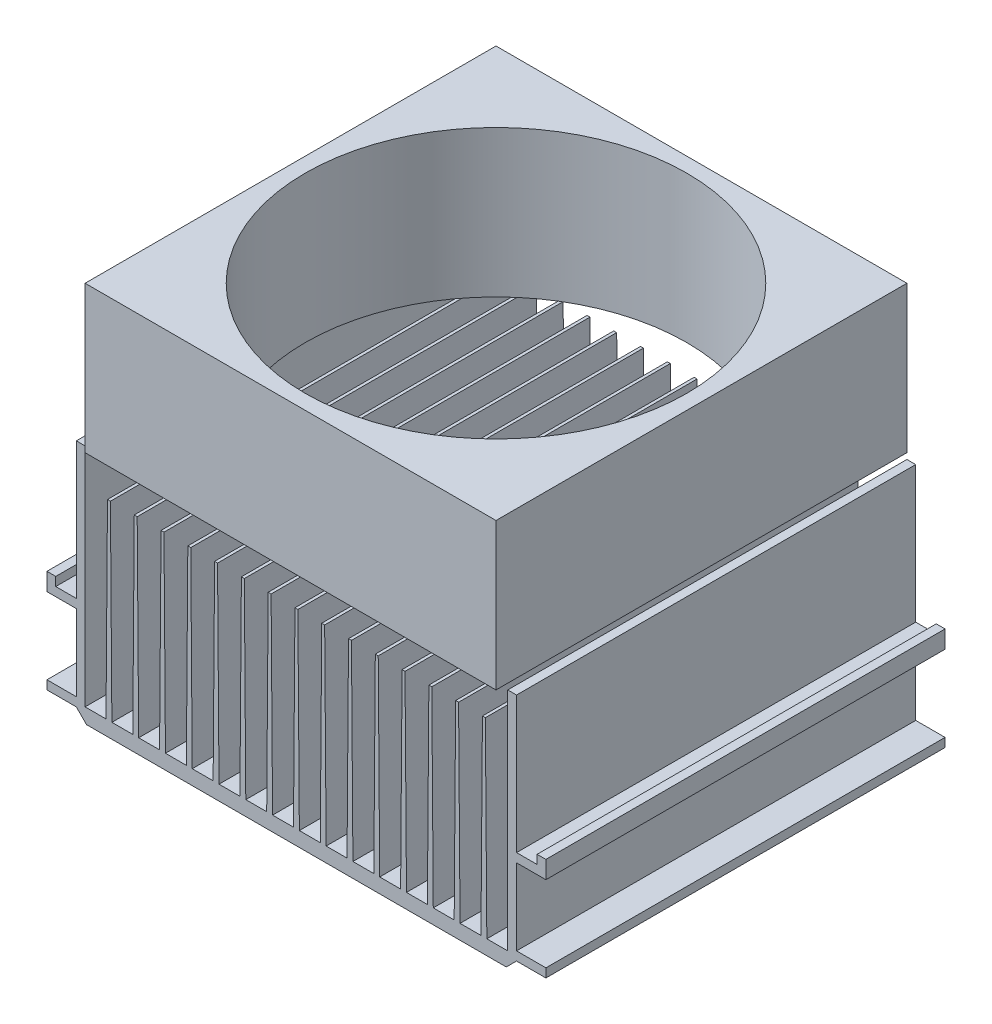
SolidWorks part; units mm, degrees
material "1060 Alloy"
ref_plane "Front Plane" through (0, 0, 0) normal (0, 0, 1) x (1, 0, 0)
ref_plane "Top Plane" through (0, 0, 0) normal (0, 1, 0) x (1, 0, 0)
ref_plane "Right Plane" through (0, 0, 0) normal (1, 0, 0) x (0, 0, -1)
sketch "Sketch1" plane through (0, 0, 0) normal (0, 0, 1) x (1, 0, 0)
  line L0 (0, 0) -> (0, 21.4242) construction
  line L1 (-35.75, 0) -> (35.75, 0)
  line L2 (35.75, 0) -> (37.5, 1.75)
  line L3 (37.5, 1.75) -> (42.5, 1.75)
  line L4 (42.5, 1.75) -> (42.5, 3.25)
  line L5 (42.5, 3.25) -> (37.5, 3.25)
  line L6 (37.5, 3.25) -> (37.5, 16.25)
  line L7 (37.5, 41) -> (36, 41)
  line L8 (36, 41) -> (36, 2.5)
  line L9 (36, 2.5) -> (32.4375, 2.5)
  line L10 (32.4375, 2.5) -> (32.1875, 35)
  line L11 (32.1875, 35) -> (31.6875, 35)
  line L12 (31.6875, 35) -> (31.4375, 2.5)
  line L13 (31.4375, 2.5) -> (27.875, 2.5)
  line L14 (31.6875, 35) -> (31.6875, 2.5) construction
  line L15 (31.6875, 2.5) -> (31.4375, 2.5) construction
  line L16 (32.1875, 35) -> (32.1875, 2.5) construction
  line L17 (32.1875, 2.5) -> (32.4375, 2.5) construction
  line L18 (31.6875, 2.5) -> (32.1875, 2.5) construction
  line L19 (37.5, 16.25) -> (42.5, 16.25)
  line L20 (42.5, 16.25) -> (42.5, 19.25)
  line L21 (42.5, 19.25) -> (41, 19.25)
  line L22 (41, 19.25) -> (41, 17.75)
  line L23 (41, 17.75) -> (37.5, 17.75)
  line L24 (37.5, 17.75) -> (37.5, 41)
  line L25 (37.5, 17.75) -> (37.5, 16.25) construction
  line L26 (37.5, 3.25) -> (37.5, 2.5) construction
  line L27 (37.5, 2.5) -> (37.5, 1.75) construction
  line L28 (37.5, 2.5) -> (36, 2.5) construction
  line L29 (27.875, 2.5) -> (27.625, 35)
  line L30 (27.125, 35) -> (26.875, 2.5)
  line L31 (27.625, 35) -> (27.125, 35)
  line L32 (26.875, 2.5) -> (23.3125, 2.5)
  line L33 (23.3125, 2.5) -> (23.0625, 35)
  line L34 (22.5625, 35) -> (22.3125, 2.5)
  line L35 (23.0625, 35) -> (22.5625, 35)
  line L36 (22.3125, 2.5) -> (18.75, 2.5)
  line L37 (18.75, 2.5) -> (18.5, 35)
  line L38 (18, 35) -> (17.75, 2.5)
  line L39 (18.5, 35) -> (18, 35)
  line L40 (17.75, 2.5) -> (14.1875, 2.5)
  line L41 (14.1875, 2.5) -> (13.9375, 35)
  line L42 (13.4375, 35) -> (13.1875, 2.5)
  line L43 (13.9375, 35) -> (13.4375, 35)
  line L44 (13.1875, 2.5) -> (9.625, 2.5)
  line L45 (9.625, 2.5) -> (9.375, 35)
  line L46 (8.875, 35) -> (8.625, 2.5)
  line L47 (9.375, 35) -> (8.875, 35)
  line L48 (8.625, 2.5) -> (5.0625, 2.5)
  line L49 (5.0625, 2.5) -> (4.8125, 35)
  line L50 (4.3125, 35) -> (4.0625, 2.5)
  line L51 (4.8125, 35) -> (4.3125, 35)
  line L52 (0.5, 2.5) -> (0, 2.5) construction
  line L53 (0, 2.5) -> (-0.5, 2.5) construction
  line L54 (4.0625, 2.5) -> (0.5, 2.5)
  line L55 (0.5, 2.5) -> (0.25, 35)
  line L56 (-0.25, 35) -> (-0.5, 2.5)
  line L57 (0.25, 35) -> (-0.25, 35)
  line L58 (-4.0625, 2.5) -> (-0.5, 2.5)
  line L59 (-4.3125, 35) -> (-4.0625, 2.5)
  line L60 (-4.8125, 35) -> (-4.3125, 35)
  line L61 (-5.0625, 2.5) -> (-4.8125, 35)
  line L62 (-8.625, 2.5) -> (-5.0625, 2.5)
  line L63 (-8.875, 35) -> (-8.625, 2.5)
  line L64 (-9.375, 35) -> (-8.875, 35)
  line L65 (-9.625, 2.5) -> (-9.375, 35)
  line L66 (-13.1875, 2.5) -> (-9.625, 2.5)
  line L67 (-13.4375, 35) -> (-13.1875, 2.5)
  line L68 (-13.9375, 35) -> (-13.4375, 35)
  line L69 (-14.1875, 2.5) -> (-13.9375, 35)
  line L70 (-17.75, 2.5) -> (-14.1875, 2.5)
  line L71 (-18, 35) -> (-17.75, 2.5)
  line L72 (-18.5, 35) -> (-18, 35)
  line L73 (-18.75, 2.5) -> (-18.5, 35)
  line L74 (-22.3125, 2.5) -> (-18.75, 2.5)
  line L75 (-22.5625, 35) -> (-22.3125, 2.5)
  line L76 (-23.0625, 35) -> (-22.5625, 35)
  line L77 (-23.3125, 2.5) -> (-23.0625, 35)
  line L78 (-26.875, 2.5) -> (-23.3125, 2.5)
  line L79 (-27.125, 35) -> (-26.875, 2.5)
  line L80 (-27.625, 35) -> (-27.125, 35)
  line L81 (-27.875, 2.5) -> (-27.625, 35)
  line L82 (-31.4375, 2.5) -> (-27.875, 2.5)
  line L83 (-31.6875, 35) -> (-31.4375, 2.5)
  line L84 (-32.1875, 35) -> (-31.6875, 35)
  line L85 (-32.4375, 2.5) -> (-32.1875, 35)
  line L86 (-36, 2.5) -> (-32.4375, 2.5)
  line L87 (-36, 41) -> (-36, 2.5)
  line L88 (-37.5, 41) -> (-36, 41)
  line L89 (-37.5, 17.75) -> (-37.5, 41)
  line L90 (-41, 17.75) -> (-37.5, 17.75)
  line L91 (-41, 19.25) -> (-41, 17.75)
  line L92 (-42.5, 19.25) -> (-41, 19.25)
  line L93 (-42.5, 16.25) -> (-42.5, 19.25)
  line L94 (-37.5, 16.25) -> (-42.5, 16.25)
  line L95 (-37.5, 3.25) -> (-37.5, 16.25)
  line L96 (-42.5, 3.25) -> (-37.5, 3.25)
  line L97 (-42.5, 1.75) -> (-42.5, 3.25)
  line L98 (-37.5, 1.75) -> (-42.5, 1.75)
  line L99 (-35.75, 0) -> (-37.5, 1.75)
  point P96 (0, 0)
  dimension "D1" = 42.5
  dimension "D2" = 41
  dimension "D3" = 2.5
  dimension "D4" = 1.5
  dimension "D5" = 1.5
  dimension "D6" = 5
  dimension "D8" = 0.5
  dimension "D9" = 1
  dimension "D10" = 45
  dimension "D11" = 35
  dimension "D12" = 16
  dimension "D13" = 8
extrude "Heatsink" add sketch "Sketch1" against normal blind 68
sketch "Sketch3" plane through (0, 41, 0) normal (0, 1, 0) x (1, 0, 0)
  line L0 (0, 0) -> (0, 1.5243) construction
  line L1 (-35, 69) -> (35, 69)
  line L2 (0, 0) -> (2.5943, 0) construction
  line L3 (17.5, -1) -> (17.5, 0) construction
  line L4 (-35, 69) -> (-35, -1)
  line L5 (-35, -1) -> (0, -1)
  line L6 (35, 69) -> (35, -1)
  line L7 (0, -1) -> (35, -1)
  line L8 (17.5, 69) -> (17.5, 68) construction
  line L9 (17.75, 68) -> (14.1875, 68) construction
  line L10 (35, 34) -> (-35, 34) construction
  circle A0 centre (0, 34) radius 32.5
  dimension "D2" = 65
  dimension "D1" = 70
extrude "Fan" add sketch "Sketch3" along normal blind 25 separate body
equation "\"D1@Sketch1\"=85/2"
